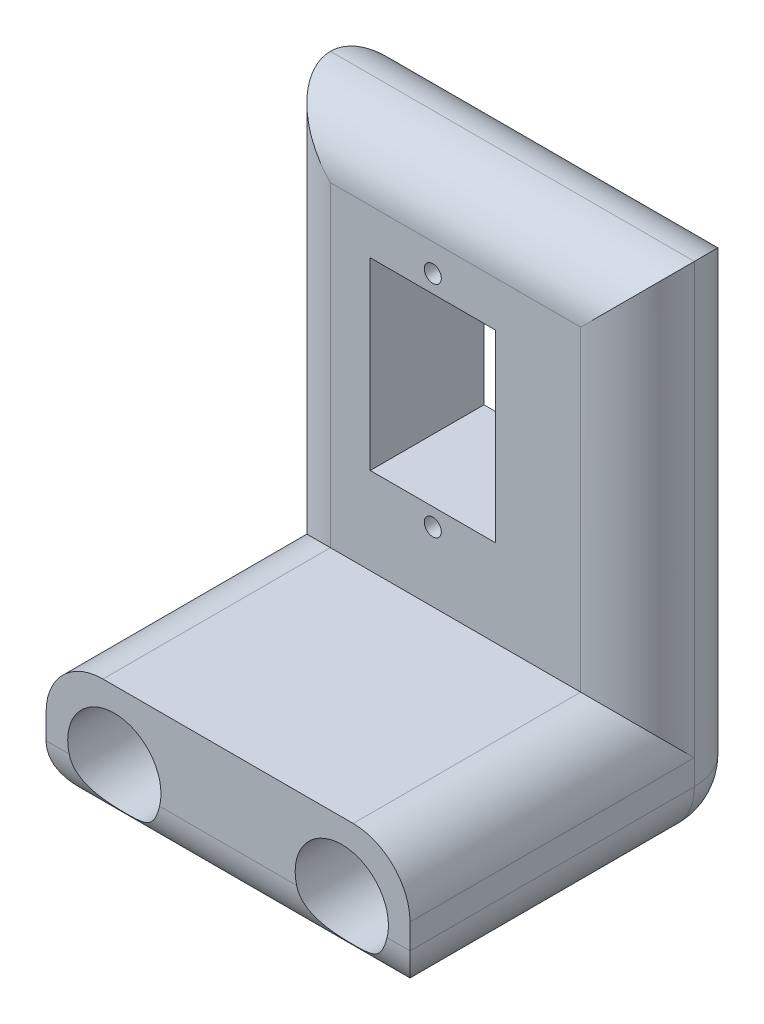
SolidWorks part; units mm, degrees
material "Polyetheretherketone (PEEK)"
ref_plane "Front Plane" through (0, 0, 0) normal (0, 0, 1) x (1, 0, 0)
ref_plane "Top Plane" through (0, 0, 0) normal (0, 1, 0) x (1, 0, 0)
ref_plane "Right Plane" through (0, 0, 0) normal (1, 0, 0) x (0, 0, -1)
sketch "Sketch1" plane through (0, 0, 0) normal (0, 0, 1) x (1, 0, 0)
  line L0 (-16, 0) -> (16, 0)
  line L1 (16, 0) -> (16, 45)
  line L2 (16, 45) -> (-16, 45)
  line L3 (-16, 45) -> (-16, 0)
  point P2 (0, 0)
  dimension "D1" = 32
  dimension "D2" = 45
extrude "Boss-Extrude1" add sketch "Sketch1" along normal mid plane 50
sketch "Sketch2" plane through (0, 0, 25) normal (0, 0, 1) x (1, 0, 0)
  line L0 (0, 0) -> (0, 45) construction
  line L1 (16, 45) -> (-16, 45) construction
  line L2 (-16, 0) -> (16, 0) construction
  circle A0 centre (10, 6) radius 4.1
  circle A1 centre (-10, 6) radius 4.1
  circle A2 centre (0, 27.9274) radius 20 construction
  dimension "D3" = 8.2
  dimension "D4" = 40
  dimension "D1" = 6
  dimension "D2" = 10
  dimension "D5" = 27.9274
extrude "Cut-Extrude1" cut sketch "Sketch2" against normal blind 20
sketch "Sketch3" plane through (0, 0, 25) normal (0, 0, 1) x (1, 0, 0)
  line L0 (-16, 12.2) -> (16, 12.2)
  line L1 (-16, 45) -> (-16, 0) construction
  line L2 (16, 0) -> (16, 45) construction
  line L3 (16, 12.2) -> (16, 45)
  line L4 (16, 45) -> (-16, 45)
  line L5 (-16, 45) -> (-16, 12.2)
  line L6 (-16, 0) -> (16, 0) construction
  dimension "D1" = 12.2
extrude "Cut-Extrude2" cut sketch "Sketch3" against normal blind 20
sketch "Sketch4" plane through (0, 0, 5) normal (0, 0, 1) x (1, 0, 0)
  line L0 (0, 12.2) -> (0, 45) construction
  line L1 (-16, 12.2) -> (16, 12.2) construction
  line L2 (16, 45) -> (-16, 45) construction
  line L3 (-2, 45) -> (-2, 12.2) construction
  line L4 (-16, 27.93) -> (16, 27.93) construction
  line L5 (-16, 45) -> (-16, 12.2) construction
  line L6 (16, 12.2) -> (16, 45) construction
  line L7 (-16, 0) -> (16, 0) construction
  line L8 (-7.5, 19.83) -> (3.5, 19.83)
  line L9 (3.5, 19.83) -> (3.5, 36.03)
  line L10 (3.5, 36.03) -> (-7.5, 36.03)
  line L11 (-7.5, 36.03) -> (-7.5, 19.83)
  circle A0 centre (-2, 37.58) radius 0.75
  circle A1 centre (-2, 18.28) radius 0.75
  point P13 (-2, 19.83)
  dimension "D2" = 1.5
  dimension "D3" = 19.3
  dimension "D1" = 2
  dimension "D4" = 27.93
  dimension "D5" = 11
  dimension "D6" = 16.2
extrude "Cut-Extrude3" cut sketch "Sketch4" against normal through all
sketch "Sketch5" plane through (-16, 0, 0) normal (-1, 0, 0) x (0, 0, 1)
  line L0 (-5, 45) -> (-5, 0)
  line L1 (5, 45) -> (-25, 45) construction
  line L2 (25, 0) -> (-25, 0) construction
  line L3 (-25, 0) -> (-25, 45)
  line L4 (-25, 45) -> (-5, 45)
  line L5 (5, 45) -> (5, 12.2) construction
  line L6 (-5, 0) -> (-25, 0)
  dimension "D1" = 10
extrude "Cut-Extrude5" cut sketch "Sketch5" against normal through all
fillet "Fillet1" radius 5 12 edges at (16, 12.2, 15) (0, 0, -5) (0, 45, -5) (-16, 22.5, -5) (16, 22.5, -5) (16, 0, 10) (-16, 0, 10) (0, 0, 25) (-16, 12.2, 15) (16, 28.6, 5) (0, 45, 5) (-16, 28.6, 5)
